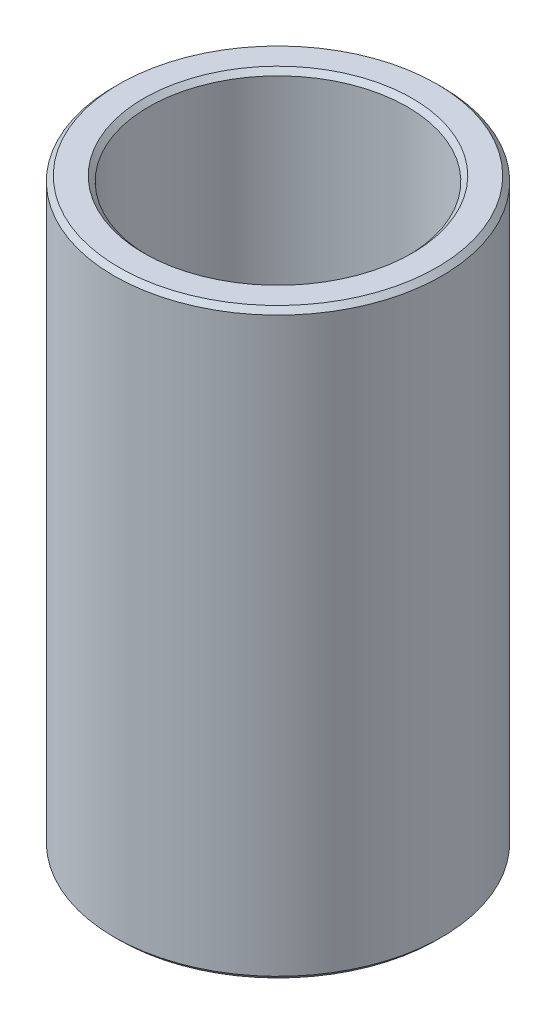
SolidWorks part; units mm, degrees
ref_plane "Front Plane" through (0, 0, 0) normal (0, 0, 1) x (1, 0, 0)
ref_plane "Top Plane" through (0, 0, 0) normal (0, 1, 0) x (1, 0, 0)
ref_plane "Right Plane" through (0, 0, 0) normal (1, 0, 0) x (0, 0, -1)
sketch "Sketch1" plane through (0, 0, 0) normal (0, 1, 0) x (1, 0, 0)
  circle A0 centre (0, 0) radius 47.5
  dimension "SLEEVE_OD" = 95
extrude "Boss-Extrude1" add sketch "Sketch1" along normal blind 168.8767
sketch "Sketch2" plane through (0, 0, 0) normal (0, 1, 0) x (1, 0, 0)
  circle A0 centre (0, 0) radius 37.4895
  dimension "BORE_D" = 74.979
extrude "Cut-Extrude1" cut sketch "Sketch2" along normal through all
chamfer "Chamfer1" distance 1.4231 angle 45 4 edges at (0, 168.8767, 37.4895) (0, 0, 37.4895) (0, 0, 47.5) (0, 168.8767, 47.5)
